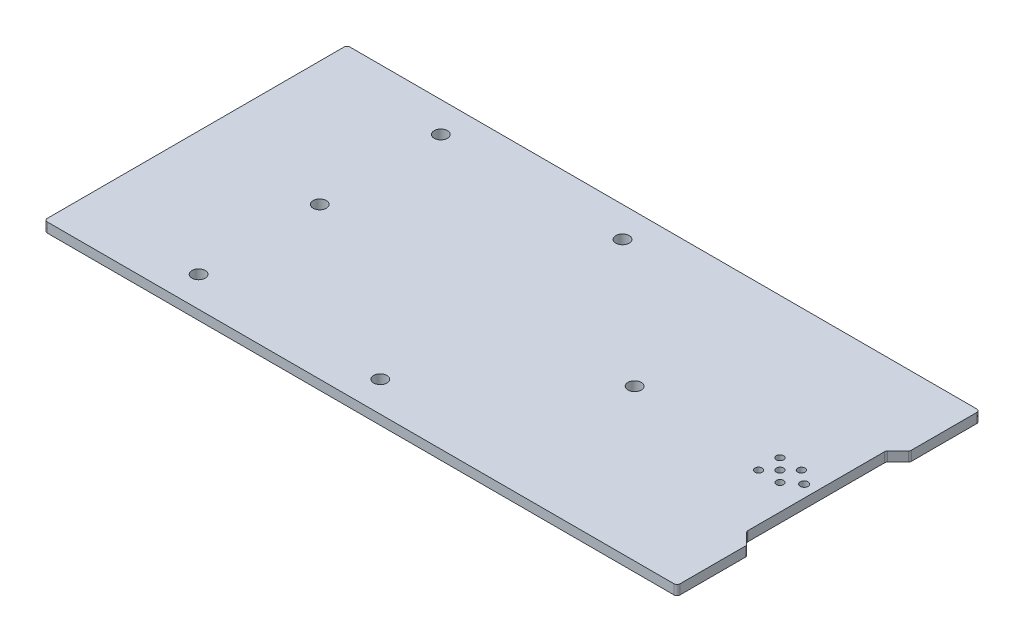
SolidWorks part; units mm, degrees
ref_plane "Front Plane" through (0, 0, 0) normal (0, 0, 1) x (1, 0, 0)
ref_plane "Top Plane" through (0, 0, 0) normal (0, 1, 0) x (1, 0, 0)
ref_plane "Right Plane" through (0, 0, 0) normal (1, 0, 0) x (0, 0, -1)
sketch "Sketch1" plane through (0, 0, 0) normal (0, 1, 0) x (1, 0, 0)
  line L0 (102.5, 50) -> (103.9926, 50)
  line L1 (0.5074, 0) -> (102.5, 0)
  line L2 (0, 0.5074) -> (0, 49.4926)
  line L3 (0.5074, 50) -> (102.5, 50)
  line L4 (102.5, 13.7102) -> (102.5, 36.2898)
  line L5 (104.5, 49.4926) -> (104.5, 38.7102)
  line L6 (104.3514, 38.3514) -> (102.6486, 36.6486)
  line L7 (0, 25) -> (160.2024, 25) construction
  line L8 (104.3514, 11.6486) -> (102.6486, 13.3514)
  line L9 (102.5, 0) -> (103.9926, 0)
  line L10 (104.5, 0.5074) -> (104.5, 11.2898)
  arc A0 (0.5074, 0) -> (0, 0.5074) centre (0.5074, 0.5074) cw
  arc A1 (0, 49.4926) -> (0.5074, 50) centre (0.5074, 49.4926) cw
  arc A2 (103.9926, 0) -> (104.5, 0.5074) centre (103.9926, 0.5074) ccw
  arc A3 (104.3514, 11.6486) -> (104.5, 11.2898) centre (103.9926, 11.2898) cw
  arc A4 (102.6486, 13.3514) -> (102.5, 13.7102) centre (103.0074, 13.7102) cw
  arc A5 (102.6486, 36.6486) -> (102.5, 36.2898) centre (103.0074, 36.2898) ccw
  arc A6 (104.5, 38.7102) -> (104.3514, 38.3514) centre (103.9926, 38.7102) cw
  arc A7 (103.9926, 50) -> (104.5, 49.4926) centre (103.9926, 49.4926) cw
  point P16 (0, 0)
  point P21 (104.5, 0)
  point P24 (104.5, 11.5)
  point P27 (102.5, 13.5)
  point P30 (102.5, 36.5)
  point P33 (104.5, 38.5)
  point P36 (104.5, 50)
  dimension "D6" = 0.5074
  dimension "D1" = 50
  dimension "D2" = 102.5
  dimension "D3" = 11.5
  dimension "D4" = 2
  dimension "D5" = 2
extrude "Boss-Extrude1" add sketch "Sketch1" along normal blind 1.6 contours L1 L9 A2 L10 A3 L8 A4 L4 A5 L6 A6 L5 A7 L0 L3 A1 L2 A0
sketch "Sketch2" plane through (0, 1.6, 0) normal (0, 1, 0) x (1, 0, 0)
  line L0 (0, 0.5074) -> (0, 49.4926) construction
  line L1 (0.5074, 0) -> (103.9926, 0) construction
  circle A0 centre (20.5, 5) radius 1.1
  circle A1 centre (20.5, 25) radius 1.1
  circle A2 centre (20.5, 45) radius 1.1
  circle A3 centre (50.5, 45) radius 1.1
  circle A4 centre (50.5, 5) radius 1.1
  circle A5 centre (72.5, 25) radius 1.1
  dimension "D1" = 2.2
  dimension "D2" = 20.5
  dimension "D3" = 5
  dimension "D4" = 25
  dimension "D5" = 45
  dimension "D6" = 50.5
  dimension "D7" = 72.5
extrude "Cut-Extrude1" cut sketch "Sketch2" against normal through all
sketch "Sketch3" plane through (0, 1.6, 0) normal (0, 1, 0) x (1, 0, 0)
  line L0 (94.7322, 26.7678) -> (98.2678, 23.2322) construction
  line L1 (94.7322, 23.2322) -> (98.2678, 26.7678) construction
  line L2 (0, 0.5074) -> (0, 49.4926) construction
  circle A0 centre (96.5, 25) radius 0.6
  circle A1 centre (96.5, 25) radius 2.5 construction
  circle A2 centre (94.7322, 26.7678) radius 0.6
  circle A3 centre (98.2678, 26.7678) radius 0.6
  circle A4 centre (98.2678, 23.2322) radius 0.6
  circle A5 centre (94.7322, 23.2322) radius 0.6
  circle A6 centre (100.5, 25) radius 0.65
  point P15 (0, 25)
  dimension "D1" = 1.2
  dimension "D2" = 1.3
  dimension "D5" = 5
  dimension "D3" = 4
  dimension "D4" = 96.5
extrude "M12 mounting holes" cut sketch "Sketch3" against normal up to next
